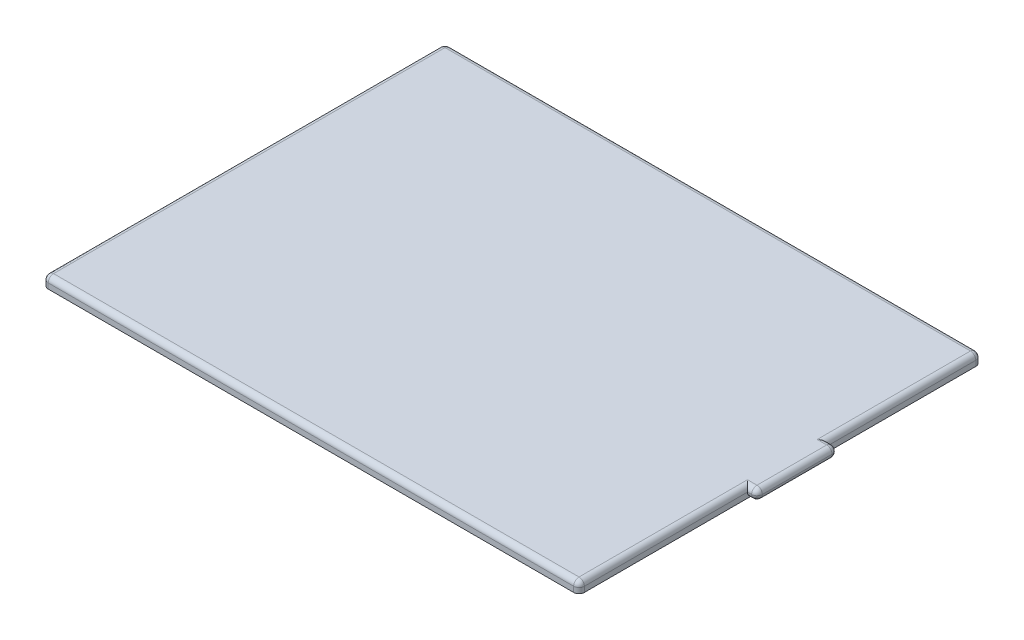
SolidWorks part; units mm, degrees
ref_plane "Front Plane" through (0, 0, 0) normal (0, 0, 1) x (1, 0, 0)
ref_plane "Top Plane" through (0, 0, 0) normal (0, 1, 0) x (1, 0, 0)
ref_plane "Right Plane" through (0, 0, 0) normal (1, 0, 0) x (0, 0, -1)
sketch "Sketch1" plane through (0, 0, 0) normal (0, 1, 0) x (1, 0, 0)
  line L5 (-206.4103, 94.7115) -> (-6.4103, 94.7115)
  line L6 (-206.4103, 94.7115) -> (-206.4103, -55.2885)
  line L7 (-206.4103, -55.2885) -> (-6.4103, -55.2885)
  line L8 (-6.4103, 94.7115) -> (-6.4103, -55.2885)
  line L9 (-206.4103, 94.7115) -> (-6.4103, -55.2885) construction
  line L10 (-206.4103, -55.2885) -> (-6.4103, 94.7115) construction
  point P0 (-106.4103, 19.7115)
  dimension "D1" = 200
  dimension "D2" = 150
extrude "Boss-Extrude1" add sketch "Sketch1" along normal blind 4
fillet "Fillet1" radius 2 2 edges at (-206.4103, 4, -19.7115) (-106.4103, 4, -94.7115)
fillet "Fillet2" radius 2 3 edges at (-206.4103, 1, 55.2885) (-205.8245, 3.4142, 55.2885) (-105.4103, 4, 55.2885)
fillet "Fillet3" radius 2 5 edges at (-6.4103, 1, 55.2885) (-6.4103, 3.4142, 54.7027) (-6.4103, 1, -94.7115) (-6.4103, 3.4142, -94.1258) (-6.4103, 4, -19.7115)
fillet "Fillet4" radius 2 2 edges at (-206.4103, 1, -94.7115) (-205.8245, 3.4142, -94.1258)
sketch "Sketch2" plane through (0, 4, 0) normal (0, 1, 0) x (1, 0, 0)
  line L0 (-10.8659, 94.7115) -> (-10.8659, -55.2885) construction
  line L1 (-204.4103, 94.7115) -> (-8.4103, 94.7115) construction
  line L2 (-8.4103, -55.2885) -> (-204.4103, -55.2885) construction
  line L3 (-10.8659, -55.2885) -> (-10.8659, 22.5491) construction
  line L4 (-10.8659, 22.5491) -> (20.0456, 22.5491) construction
  line L6 (-10.8659, 37.5491) -> (-2.8659, 37.5491)
  line L7 (-10.8659, 37.5491) -> (-10.8659, 7.5491)
  line L8 (-10.8659, 7.5491) -> (-2.8659, 7.5491)
  line L9 (-2.8659, 37.5491) -> (-2.8659, 7.5491)
  dimension "D1" = 30
  dimension "D2" = 15
  dimension "D3" = 8
extrude "Boss-Extrude2" add sketch "Sketch2" against normal blind 4
fillet "Fillet5" radius 2 6 edges at (-4.6381, 0, -37.5491) (-4.6381, 0, -7.5491) (-5.6381, 4, -7.5491) (-5.6381, 4, -37.5491) (-2.8659, 4, -22.5491) (-2.8659, 0, -22.5491)
